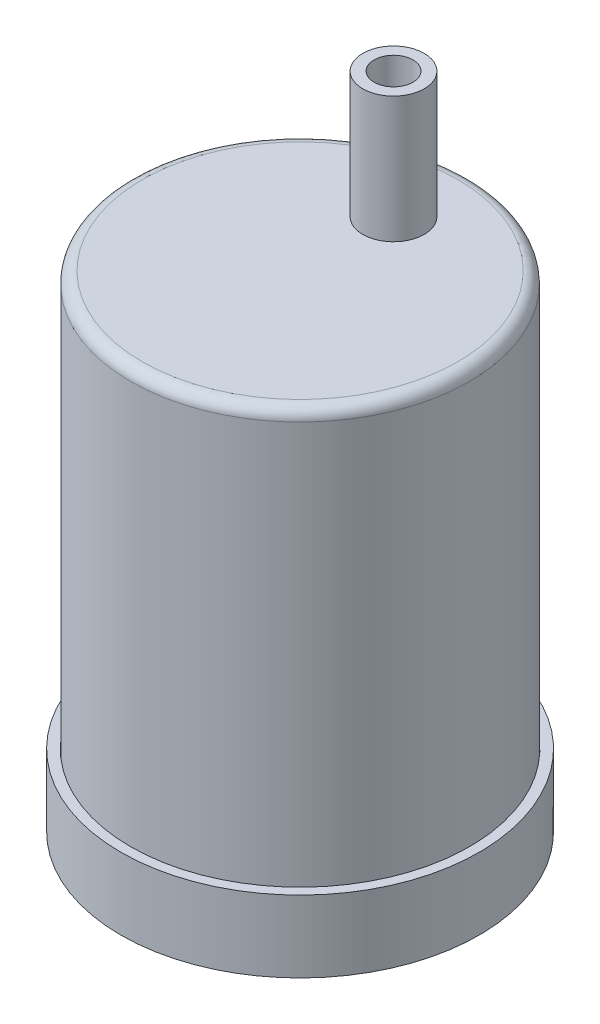
SolidWorks part; units mm, degrees
ref_plane "Front Plane" through (0, 0, 0) normal (0, 0, 1) x (1, 0, 0)
ref_plane "Top Plane" through (0, 0, 0) normal (0, 1, 0) x (1, 0, 0)
ref_plane "Right Plane" through (0, 0, 0) normal (1, 0, 0) x (0, 0, -1)
sketch "Sketch1" plane through (0, 0, 0) normal (0, 1, 0) x (1, 0, 0)
  circle A0 centre (0, 0) radius 19.85
  circle A1 centre (0, 0) radius 18.78
  circle A2 centre (0, 0) radius 12.5
  dimension "D1" = 39.7
  dimension "D2" = 1.07
  dimension "D3" = 25
extrude "Boss-Extrude3" add sketch "Sketch1" along normal blind 7.95 contours A0 | A1
sketch "Sketch2" plane through (0, 0, 0) normal (0, -1, 0) x (1, 0, 0)
  circle A0 centre (0, 0) radius 18.78
extrude "Boss-Extrude5" add sketch "Sketch2" against normal blind 1.5
sketch "Sketch4" plane through (0, 0, 0) normal (0, -1, 0) x (1, 0, 0)
  circle A0 centre (0, 0) radius 12.5
extrude "Boss-Extrude6" add sketch "Sketch4" against normal blind 16.31 separate body
sketch "Sketch5" plane through (0, 16.31, 0) normal (0, 1, 0) x (1, 0, 0)
  line L1 (2.15, 10.35) -> (-2.15, 10.35)
  line L2 (2.15, 10.35) -> (2.15, 12.5)
  line L3 (2.15, 12.5) -> (-2.15, 12.5)
  line L4 (-2.15, 10.35) -> (-2.15, 12.5)
  circle A2 centre (0, 10.35) radius 2.15
extrude "Cut-Extrude2" cut sketch "Sketch5" against normal blind 16.31 contours L2 L3 L4 L1 | A2
sketch "Sketch6" plane through (0, 0, 0) normal (0, -1, 0) x (1, 0, 0)
  circle A0 centre (0, 0) radius 11.5974
extrude "Cut-Extrude3" cut sketch "Sketch6" against normal blind 14.81
sketch "Sketch12" plane through (0, 16.31, 0) normal (0, 1, 0) x (1, 0, 0)
  line L1 (3.4, 10.35) -> (-3.4, 10.35)
  line L2 (3.4, 10.35) -> (3.4, 13.75)
  line L3 (3.4, 13.75) -> (-3.4, 13.75)
  line L4 (-3.4, 10.35) -> (-3.4, 13.75)
  circle A0 centre (0, 10.35) radius 3.4
  arc A1 (-2.15, 10.35) -> (2.15, 10.35) centre (0, 10.35) ccw construction
  dimension "D1" = 1.25
extrude "Boss-Extrude8" add sketch "Sketch12" against normal blind 24.97 contours L2 L3 L4 L1 | A0
extrude "Cut-Extrude5" cut sketch "Sketch5<6>" against normal blind 24.97 contours L1 A2 | L3 L4 L1 L2 region at (0, 16.31, -9.4375)
sketch "Sketch5<6>" plane through (0, 16.31, 0) normal (0, 1, 0) x (1, 0, 0) same geometry as "Sketch5"
sketch "Sketch14" plane through (0, 16.31, 0) normal (0, 1, 0) x (1, 0, 0)
  circle A0 centre (0, 0) radius 12.5
  circle A1 centre (0, 0) radius 15.2193
extrude "Cut-Extrude6" cut sketch "Sketch14" against normal up to vertex (14.81 mm away) up to point (3.4, 1.5, -12.0287)
sketch "Sketch17" plane through (0, 0, 0) normal (0, -1, 0) x (1, 0, 0)
  line L1 (3.4, -11.0878) -> (-3.4, -11.0878)
  line L2 (3.4, -11.0878) -> (3.4, -13.75)
  line L3 (3.4, -13.75) -> (-3.4, -13.75)
  line L4 (-3.4, -11.0878) -> (-3.4, -13.75)
extrude "Cut-Extrude7" cut sketch "Sketch17" along normal blind 16.588
sketch "Sketch18" plane through (0, 0, 0) normal (0, -1, 0) x (1, 0, 0)
  circle A0 centre (0, -10.35) radius 2.15
  circle A1 centre (0, -10.35) radius 3.4
  arc A2 (2.15, -10.35) -> (-2.15, -10.35) centre (0, -10.35) ccw construction
  arc A3 (3.4, -10.35) -> (-3.4, -10.35) centre (0, -10.35) ccw construction
  dimension "D1" = 0
  dimension "D2" = 0
extrude "Boss-Extrude10" add sketch "Sketch18" along normal blind 14
sketch "Sketch19" plane through (0, 0, 0) normal (0, -1, 0) x (1, 0, 0)
  circle A0 centre (0, -10.35) radius 3.4
  circle A1 centre (0, -10.35) radius 5.6182
  arc A2 (-3.319, -11.0878) -> (3.319, -11.0878) centre (0, -10.35) ccw construction
  dimension "D1" = 0
extrude "Cut-Extrude8" cut sketch "Sketch19" along normal blind 14
sketch "Sketch20" plane through (0, 1.5, 0) normal (0, 1, 0) x (1, 0, 0)
  circle A0 centre (0, 0) radius 18.78 construction
  circle A1 centre (0, 0) radius 18.78 construction
  circle A2 centre (0, 0) radius 18.7419
  circle A3 centre (0, 0) radius 17.5419
  dimension "D1" = 0.0381
  dimension "D2" = 1.2
extrude "Boss-Extrude11" add sketch "Sketch20" along normal blind 50.8 separate body
sketch "Sketch21" plane through (0, 52.3, 0) normal (0, 1, 0) x (1, 0, 0)
  circle A0 centre (0, 0) radius 18.7419 construction
  circle A1 centre (0, 0) radius 18.7419
extrude "Boss-Extrude12" add sketch "Sketch21" along normal blind 1.5
sketch "Sketch22" plane through (0, 53.8, 0) normal (0, 1, 0) x (1, 0, 0)
  circle A0 centre (0, 10.35) radius 3.4 construction
  circle A1 centre (0, 10.35) radius 3.4
  circle A2 centre (0, 10.35) radius 2.15 construction
  circle A3 centre (0, 10.35) radius 2.15
extrude "Boss-Extrude13" add sketch "Sketch22" along normal blind 13.97
sketch "Sketch23" plane through (0, 67.77, 0) normal (0, 1, 0) x (1, 0, 0)
  circle A0 centre (0, 10.35) radius 2.15 construction
  circle A1 centre (0, 10.35) radius 2.15
extrude "Cut-Extrude9" cut sketch "Sketch23" against normal blind 30.456
fillet "Fillet1" radius 1.27 1 edges at (0, 52.3, 17.5419)
fillet "Fillet2" radius 1.27 1 edges at (0, 53.8, 18.7419)
